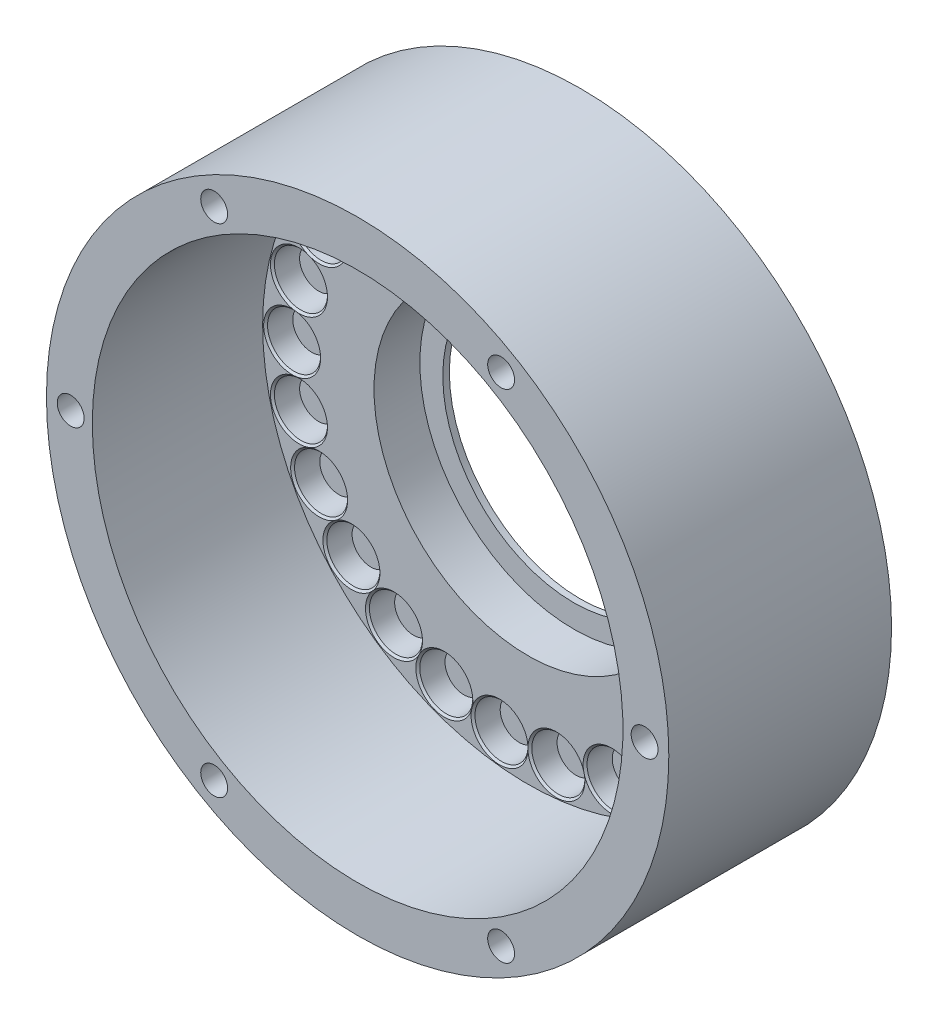
SolidWorks part; units mm, degrees
ref_plane "Front Plane" through (0, 0, 0) normal (0, 0, 1) x (1, 0, 0)
ref_plane "Top Plane" through (0, 0, 0) normal (0, 1, 0) x (1, 0, 0)
ref_plane "Right Plane" through (0, 0, 0) normal (1, 0, 0) x (0, 0, -1)
sketch "Sketch1" plane through (0, 0, 0) normal (0, 0, 1) x (1, 0, 0)
  circle A0 centre (0, 0) radius 36 construction
  circle A1 centre (36, 0) radius 4.05
  circle A2 centre (34.9539, -8.6154) radius 4.05
  circle A3 centre (31.8764, -16.73) radius 4.05
  circle A4 centre (26.9464, -23.8724) radius 4.05
  circle A5 centre (20.4503, -29.6274) radius 4.05
  circle A6 centre (12.7658, -33.6606) radius 4.05
  circle A7 centre (4.3393, -35.7375) radius 4.05
  circle A8 centre (-4.3393, -35.7375) radius 4.05
  circle A9 centre (-12.7658, -33.6606) radius 4.05
  circle A10 centre (-20.4503, -29.6274) radius 4.05
  circle A11 centre (-26.9464, -23.8724) radius 4.05
  circle A12 centre (-31.8764, -16.73) radius 4.05
  circle A13 centre (-34.9539, -8.6154) radius 4.05
  circle A14 centre (-36, 0) radius 4.05
  circle A15 centre (-34.9539, 8.6154) radius 4.05
  circle A16 centre (-31.8764, 16.73) radius 4.05
  circle A17 centre (-26.9464, 23.8724) radius 4.05
  circle A18 centre (-20.4503, 29.6274) radius 4.05
  circle A19 centre (-12.7658, 33.6606) radius 4.05
  circle A20 centre (-4.3393, 35.7375) radius 4.05
  circle A23 centre (4.3393, 35.7375) radius 4.05
  circle A24 centre (0, 0) radius 47.5
  circle A25 centre (12.7658, 33.6606) radius 4.05
  circle A26 centre (20.4503, 29.6274) radius 4.05
  circle A27 centre (26.9464, 23.8724) radius 4.05
  circle A28 centre (31.8764, 16.73) radius 4.05
  circle A29 centre (34.9539, 8.6154) radius 4.05
  point P47 (0, 0)
  dimension "D1" = 8.1
  dimension "D3" = 95
  dimension "D4" = 72
  dimension "D2" = 26
extrude "Boss-Extrude1" add sketch "Sketch1" along normal blind 5
sketch "Sketch4" plane through (0, 0, 0) normal (0, 0, -1) x (-1, 0, 0)
  circle A0 centre (0, 0) radius 47.5 construction
  circle A1 centre (0, 0) radius 47.5
extrude "Boss-Extrude2" add sketch "Sketch4" along normal blind 3
sketch "Sketch5" plane through (0, 0, 0) normal (0, 0, 1) x (1, 0, 0)
  circle A0 centre (36, 0) radius 2.9
  circle A1 centre (34.9539, -8.6154) radius 2.9
  circle A2 centre (31.8764, -16.73) radius 2.9
  circle A3 centre (26.9464, -23.8724) radius 2.9
  circle A4 centre (20.4503, -29.6274) radius 2.9
  circle A5 centre (12.7658, -33.6606) radius 2.9
  circle A6 centre (4.3393, -35.7375) radius 2.9
  circle A7 centre (-4.3393, -35.7375) radius 2.9
  circle A8 centre (-12.7658, -33.6606) radius 2.9
  circle A9 centre (-20.4503, -29.6274) radius 2.9
  circle A10 centre (-26.9464, -23.8724) radius 2.9
  circle A11 centre (-31.8764, -16.73) radius 2.9
  circle A12 centre (-34.9539, -8.6154) radius 2.9
  circle A13 centre (-36, 0) radius 2.9
  circle A14 centre (-34.9539, 8.6154) radius 2.9
  circle A15 centre (-31.8764, 16.73) radius 2.9
  circle A16 centre (-26.9464, 23.8724) radius 2.9
  circle A17 centre (-20.4503, 29.6274) radius 2.9
  circle A18 centre (-12.7658, 33.6606) radius 2.9
  circle A19 centre (-4.3393, 35.7375) radius 2.9
  circle A20 centre (4.3393, 35.7375) radius 2.9
  circle A21 centre (12.7658, 33.6606) radius 2.9
  circle A22 centre (20.4503, 29.6274) radius 2.9
  circle A23 centre (26.9464, 23.8724) radius 2.9
  circle A24 centre (31.8764, 16.73) radius 2.9
  circle A25 centre (34.9539, 8.6154) radius 2.9
  point P55 (0, 0)
  dimension "D1" = 5.8
  dimension "D2" = 26
extrude "Boss-Extrude3" add sketch "Sketch5" along normal blind 2
sketch "Sketch6" plane through (0, 0, 5) normal (0, 0, 1) x (1, 0, 0)
  circle A0 centre (0, 0) radius 37.5 construction
  circle A1 centre (0, 0) radius 47.5
  circle A2 centre (0, 0) radius 47.5
  circle A5 centre (36, 0) radius 4.55
  arc A6 (37.2437, -4.3767) -> (38.3872, 3.8735) centre (36, 0) ccw
  arc A7 (38.3872, 3.8735) -> (38.1987, 5.4258) centre (38.9119, 4.7248) cw
  circle A8 centre (34.9539, 8.6154) radius 4.55
  arc A9 (38.1987, 5.4258) -> (35.1141, 13.1625) centre (34.9539, 8.6154) ccw
  arc A10 (35.1141, -13.1625) -> (38.1987, -5.4258) centre (34.9539, -8.6154) ccw
  arc A11 (38.1987, -5.4258) -> (38.3872, -3.8735) centre (38.9119, -4.7248) cw
  arc A12 (38.3872, -3.8735) -> (37.2437, 4.3767) centre (36, 0) ccw
  arc A13 (30.9437, -21.1834) -> (35.7903, -14.4097) centre (31.8764, -16.73) ccw
  arc A14 (35.7903, -14.4097) -> (36.3448, -12.9476) centre (36.6505, -13.8997) cw
  arc A15 (36.3448, -12.9476) -> (37.2089, -4.6635) centre (34.9539, -8.6154) ccw
  arc A16 (24.975, -27.9732) -> (31.3018, -22.5561) centre (26.9464, -23.8724) ccw
  arc A17 (31.3018, -22.5561) -> (32.1901, -21.2692) centre (32.2591, -22.2668) cw
  arc A18 (32.1901, -21.2692) -> (35.0116, -13.4326) centre (31.8764, -16.73) ccw
  arc A19 (17.5549, -33.1372) -> (24.9942, -29.3917) centre (20.4503, -29.6274) ccw
  arc A20 (24.9942, -29.3917) -> (26.1647, -28.3548) centre (25.9929, -29.3399) cw
  arc A21 (26.1647, -28.3548) -> (30.7796, -21.4211) centre (26.9464, -23.8724) ccw
  arc A22 (9.1145, -36.3755) -> (17.234, -34.5191) centre (12.7658, -33.6606) ccw
  arc A23 (17.234, -34.5191) -> (18.6186, -33.7924) centre (18.2161, -34.7078) cw
  arc A24 (18.6186, -33.7924) -> (24.7588, -28.1647) centre (20.4503, -29.6274) ccw
  arc A25 (0.1444, -37.4997) -> (8.4723, -37.6405) centre (4.3393, -35.7375) ccw
  arc A26 (8.4723, -37.6405) -> (9.9906, -37.2662) centre (9.3806, -38.0587) cw
  arc A27 (9.9906, -37.2662) -> (17.2991, -33.2715) centre (12.7658, -33.6606) ccw
  arc A28 (-8.834, -36.4446) -> (-0.7819, -38.5742) centre (-4.3393, -35.7375) ccw
  arc A29 (-0.7819, -38.5742) -> (0.7819, -38.5742) centre (0, -39.1977) cw
  arc A30 (0.7819, -38.5742) -> (8.834, -36.4446) centre (4.3393, -35.7375) ccw
  arc A31 (-17.2991, -33.2715) -> (-9.9906, -37.2662) centre (-12.7658, -33.6606) ccw
  arc A32 (-9.9906, -37.2662) -> (-8.4723, -37.6405) centre (-9.3806, -38.0587) cw
  arc A33 (-8.4723, -37.6405) -> (-0.1444, -37.4997) centre (-4.3393, -35.7375) ccw
  arc A34 (-24.7588, -28.1647) -> (-18.6186, -33.7924) centre (-20.4503, -29.6274) ccw
  arc A35 (-18.6186, -33.7924) -> (-17.234, -34.5191) centre (-18.2161, -34.7078) cw
  arc A36 (-17.234, -34.5191) -> (-9.1145, -36.3755) centre (-12.7658, -33.6606) ccw
  arc A37 (-30.7796, -21.4211) -> (-26.1647, -28.3548) centre (-26.9464, -23.8724) ccw
  arc A38 (-26.1647, -28.3548) -> (-24.9942, -29.3917) centre (-25.9929, -29.3399) cw
  arc A39 (-24.9942, -29.3917) -> (-17.5549, -33.1372) centre (-20.4503, -29.6274) ccw
  arc A40 (-35.0116, -13.4326) -> (-32.1901, -21.2692) centre (-31.8764, -16.73) ccw
  arc A41 (-32.1901, -21.2692) -> (-31.3018, -22.5561) centre (-32.2591, -22.2668) cw
  arc A42 (-31.3018, -22.5561) -> (-24.975, -27.9732) centre (-26.9464, -23.8724) ccw
  arc A43 (-37.2089, -4.6635) -> (-36.3448, -12.9476) centre (-34.9539, -8.6154) ccw
  arc A44 (-36.3448, -12.9476) -> (-35.7903, -14.4097) centre (-36.6505, -13.8997) cw
  arc A45 (-35.7903, -14.4097) -> (-30.9437, -21.1834) centre (-31.8764, -16.73) ccw
  arc A46 (-37.2437, 4.3767) -> (-38.3872, -3.8735) centre (-36, 0) ccw
  arc A47 (-38.3872, -3.8735) -> (-38.1987, -5.4258) centre (-38.9119, -4.7248) cw
  arc A48 (-38.1987, -5.4258) -> (-35.1141, -13.1625) centre (-34.9539, -8.6154) ccw
  arc A49 (-35.1141, 13.1625) -> (-38.1987, 5.4258) centre (-34.9539, 8.6154) ccw
  arc A50 (-38.1987, 5.4258) -> (-38.3872, 3.8735) centre (-38.9119, 4.7248) cw
  arc A51 (-38.3872, 3.8735) -> (-37.2437, -4.3767) centre (-36, 0) ccw
  arc A52 (-30.9437, 21.1834) -> (-35.7903, 14.4097) centre (-31.8764, 16.73) ccw
  arc A53 (-35.7903, 14.4097) -> (-36.3448, 12.9476) centre (-36.6505, 13.8997) cw
  arc A54 (-36.3448, 12.9476) -> (-37.2089, 4.6635) centre (-34.9539, 8.6154) ccw
  arc A55 (-24.975, 27.9732) -> (-31.3018, 22.5561) centre (-26.9464, 23.8724) ccw
  arc A56 (-31.3018, 22.5561) -> (-32.1901, 21.2692) centre (-32.2591, 22.2668) cw
  arc A57 (-32.1901, 21.2692) -> (-35.0116, 13.4326) centre (-31.8764, 16.73) ccw
  arc A58 (-17.5549, 33.1372) -> (-24.9942, 29.3917) centre (-20.4503, 29.6274) ccw
  arc A59 (-24.9942, 29.3917) -> (-26.1647, 28.3548) centre (-25.9929, 29.3399) cw
  arc A60 (-26.1647, 28.3548) -> (-30.7796, 21.4211) centre (-26.9464, 23.8724) ccw
  arc A61 (-9.1145, 36.3755) -> (-17.234, 34.5191) centre (-12.7658, 33.6606) ccw
  arc A62 (-17.234, 34.5191) -> (-18.6186, 33.7924) centre (-18.2161, 34.7078) cw
  arc A63 (-18.6186, 33.7924) -> (-24.7588, 28.1647) centre (-20.4503, 29.6274) ccw
  arc A64 (-0.1444, 37.4997) -> (-8.4723, 37.6405) centre (-4.3393, 35.7375) ccw
  arc A65 (-8.4723, 37.6405) -> (-9.9906, 37.2662) centre (-9.3806, 38.0587) cw
  arc A66 (-9.9906, 37.2662) -> (-17.2991, 33.2715) centre (-12.7658, 33.6606) ccw
  arc A67 (8.834, 36.4446) -> (0.7819, 38.5742) centre (4.3393, 35.7375) ccw
  arc A68 (0.7819, 38.5742) -> (-0.7819, 38.5742) centre (0, 39.1977) cw
  arc A69 (-0.7819, 38.5742) -> (-8.834, 36.4446) centre (-4.3393, 35.7375) ccw
  arc A70 (17.2991, 33.2715) -> (9.9906, 37.2662) centre (12.7658, 33.6606) ccw
  arc A71 (9.9906, 37.2662) -> (8.4723, 37.6405) centre (9.3806, 38.0587) cw
  arc A72 (8.4723, 37.6405) -> (0.1444, 37.4997) centre (4.3393, 35.7375) ccw
  arc A73 (24.7588, 28.1647) -> (18.6186, 33.7924) centre (20.4503, 29.6274) ccw
  arc A74 (18.6186, 33.7924) -> (17.234, 34.5191) centre (18.2161, 34.7078) cw
  arc A75 (17.234, 34.5191) -> (9.1145, 36.3755) centre (12.7658, 33.6606) ccw
  arc A76 (30.7796, 21.4211) -> (26.1647, 28.3548) centre (26.9464, 23.8724) ccw
  arc A77 (26.1647, 28.3548) -> (24.9942, 29.3917) centre (25.9929, 29.3399) cw
  arc A78 (24.9942, 29.3917) -> (17.5549, 33.1372) centre (20.4503, 29.6274) ccw
  arc A79 (35.0116, 13.4326) -> (32.1901, 21.2692) centre (31.8764, 16.73) ccw
  arc A80 (32.1901, 21.2692) -> (31.3018, 22.5561) centre (32.2591, 22.2668) cw
  arc A81 (31.3018, 22.5561) -> (24.975, 27.9732) centre (26.9464, 23.8724) ccw
  arc A82 (37.2089, 4.6635) -> (36.3448, 12.9476) centre (34.9539, 8.6154) ccw
  arc A83 (36.3448, 12.9476) -> (35.7903, 14.4097) centre (36.6505, 13.8997) cw
  arc A84 (35.7903, 14.4097) -> (30.9437, 21.1834) centre (31.8764, 16.73) ccw
  point P191 (0, 0)
  dimension "D5" = 1
  dimension "D1" = 0
  dimension "D2" = 10
  dimension "D3" = 0.5
  dimension "D4" = 0.5
  dimension "D6" = 26
sketch "Sketch8" plane through (0, 0, 5) normal (0, 0, 1) x (1, 0, 0)
  circle A2 centre (0, 0) radius 40.5
  circle A3 centre (0, 0) radius 40.5
  circle M15 centre (0, 0) radius 47.5
  dimension "D1" = 7
extrude "Boss-Extrude5" add sketch "Sketch8" along normal blind 26 contours A3 M15 region at (-46.1565, 0, 5)
sketch "Sketch9" plane through (0, 0, -3) normal (0, 0, -1) x (-1, 0, 0)
  circle A0 centre (0, 0) radius 20
  dimension "D1" = 40
extrude "Cut-Extrude1" cut sketch "Sketch9" against normal up to next
sketch "Sketch10" plane through (0, 0, 5) normal (0, 0, 1) x (1, 0, 0)
  circle A0 centre (0, 0) radius 23.5
  dimension "D1" = 47
extrude "Cut-Extrude2" cut sketch "Sketch10" against normal blind 7
sketch "Sketch11" plane through (0, 0, -3) normal (0, 0, -1) x (-1, 0, 0)
  circle A0 centre (0, 0) radius 43.8 construction
  circle A1 centre (43.8, 0) radius 2.05
  circle A2 centre (21.9, -37.9319) radius 2.05
  circle A3 centre (-21.9, -37.9319) radius 2.05
  circle A4 centre (-43.8, 0) radius 2.05
  circle A5 centre (-21.9, 37.9319) radius 2.05
  circle A6 centre (21.9, 37.9319) radius 2.05
  point P17 (0, 0)
  dimension "D1" = 87.6
  dimension "D2" = 4.1
  dimension "D3" = 6
extrude "Cut-Extrude3" cut sketch "Sketch11" against normal through all
sketch "Sketch12" plane through (0, 0, 5) normal (0, 0, 1) x (1, 0, 0)
  line L0 (0, 0) -> (0, 28.5) construction
  line L1 (0, 0) -> (28.5, 0) construction
  line L2 (0, 0) -> (8.807, 27.1051) construction
  circle A0 centre (0, 0) radius 28.5 construction
  circle A1 centre (8.807, 27.1051) radius 2.6
  circle A2 centre (-8.807, 27.1051) radius 2.6
  circle A3 centre (-8.807, -27.1051) radius 2.6
  circle A4 centre (8.807, -27.1051) radius 2.6
  dimension "D1" = 57
  dimension "D3" = 5.2
  dimension "D2" = 18
extrude "Cut-Extrude4" cut sketch "Sketch12" against normal through all
sketch "Sketch13" plane through (0, 0, -3) normal (0, 0, -1) x (-1, 0, 0)
  circle A0 centre (-21.9, 37.9319) radius 2.6
  circle A1 centre (21.9, 37.9319) radius 2.6
  circle A2 centre (43.8, 0) radius 2.6
  circle A3 centre (21.9, -37.9319) radius 2.6
  circle A4 centre (-21.9, -37.9319) radius 2.6
  circle A5 centre (-43.8, 0) radius 2.6
  point P16 (0, 0)
  dimension "D1" = 5.2
  dimension "D2" = 6
extrude "Cut-Extrude5" cut sketch "Sketch13" against normal blind 6
chamfer "Chamfer1" distance 0.3 angle 45 26 edges at (39.0039, -8.6154, 5) (35.9264, -16.73, 5) (30.9964, -23.8724, 5) (24.5003, -29.6274, 5) (16.8158, -33.6606, 5) (8.3893, -35.7375, 5) (-0.2893, -35.7375, 5) (-8.7158, -33.6606, 5) (-16.4003, -29.6274, 5) (-22.8964, -23.8724, 5) (-27.8264, -16.73, 5) (-30.9039, -8.6154, 5) (-31.95, 0, 5) (-30.9039, 8.6154, 5) (-27.8264, 16.73, 5) (-22.8964, 23.8724, 5) (-16.4003, 29.6274, 5) (-8.7158, 33.6606, 5) (-0.2893, 35.7375, 5) (8.3893, 35.7375, 5) (16.8158, 33.6606, 5) (24.5003, 29.6274, 5) (30.9964, 23.8724, 5) (35.9264, 16.73, 5) (39.0039, 8.6154, 5) (40.05, 0, 5)
sketch "Sketch14" plane through (0, 0, 5) normal (0, 0, 1) x (1, 0, 0)
  circle A0 centre (-8.807, -27.1051) radius 2.6 construction
  circle A1 centre (8.807, -27.1051) radius 2.6 construction
  circle A2 centre (8.807, 27.1051) radius 2.6 construction
  circle A3 centre (-8.807, 27.1051) radius 2.6 construction
  circle A4 centre (-8.807, -27.1051) radius 2.6
  circle A5 centre (8.807, -27.1051) radius 2.6
  circle A6 centre (8.807, 27.1051) radius 2.6
  circle A7 centre (-8.807, 27.1051) radius 2.6
extrude "Boss-Extrude6" add sketch "Sketch14" against normal blind 2
chamfer "Chamfer2" distance 0.6 angle 45 6 edges at (19.85, 37.9319, 3) (41.75, 0, 3) (19.85, -37.9319, 3) (-23.95, -37.9319, 3) (-45.85, 0, 3) (-23.95, 37.9319, 3)
